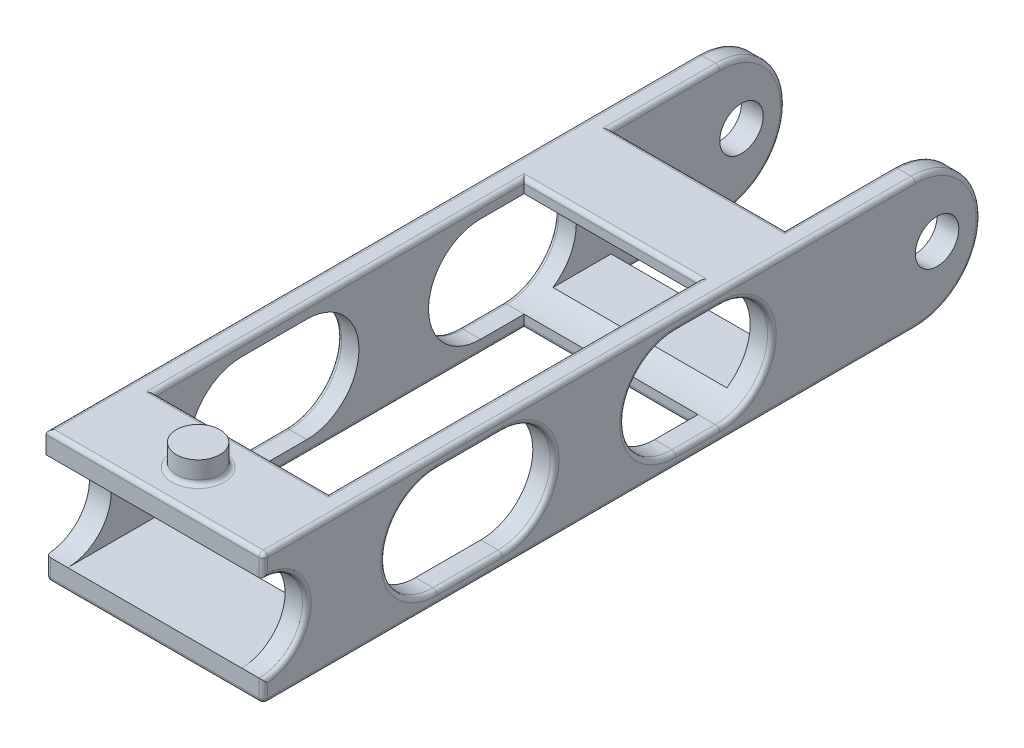
SolidWorks part; units mm, degrees
ref_plane "Front Plane" through (0, 0, 0) normal (0, 0, 1) x (1, 0, 0)
ref_plane "Top Plane" through (0, 0, 0) normal (0, 1, 0) x (1, 0, 0)
ref_plane "Right Plane" through (0, 0, 0) normal (1, 0, 0) x (0, 0, -1)
sketch "Sketch2" plane through (0, 0, 0) normal (1, 0, 0) x (0, 0, -1)
  line L1 (37.5, 7.5) -> (-37.5, 7.5)
  line L2 (37.5, 7.5) -> (37.5, -7.5)
  line L3 (37.5, -7.5) -> (-37.5, -7.5)
  line L4 (-37.5, 7.5) -> (-37.5, -7.5)
  line L5 (37.5, 7.5) -> (-37.5, -7.5) construction
  line L6 (37.5, -7.5) -> (-37.5, 7.5) construction
  arc A0 (37.5, 7.5) -> (37.5, -7.5) centre (37.5, 0) cw
  point P0 (0, 0)
  dimension "D1" = 75
  dimension "D2" = 15
extrude "Boss-Extrude1" add sketch "Sketch2" against normal blind 2.5 contours L1 L4 L3 L2 | A0 L2 region at (0, 0, 0) region at (0, 0, -40.6831)
ref_plane "Plane1" through (-12.5, 0, 0) normal (1, 0, 0) x (0, 0, -1)
sketch "Sketch3" plane through (0, 7.5, 0) normal (0, 1, 0) x (1, 0, 0)
  line L0 (-2.5, 37.5) -> (-2.5, -37.5) construction
  line L1 (-2.5, 25) -> (-22.5, 25)
  line L2 (-2.5, 25) -> (-2.5, 15)
  line L3 (-2.5, 15) -> (-22.5, 15)
  line L4 (-22.5, 25) -> (-22.5, 15)
  point P6 (-2.5, 20)
  dimension "D1" = 10
  dimension "D2" = 20
  dimension "D3" = 20
extrude "Boss-Extrude2" add sketch "Sketch3" against normal blind 2.5
mirror "Mirror2" about plane through (-12.5, 0, 0) normal (1, 0, 0) of "Boss-Extrude1"
sketch "Sketch5" plane through (0, 0, 0) normal (1, 0, 0) x (0, 0, -1)
  circle A0 centre (40, 0) radius 2.5
  dimension "D1" = 5
  dimension "D2" = 40
extrude "Cut-Extrude1" cut sketch "Sketch5" against normal through all
mirror "Mirror3" about plane through (0, 0, 0) normal (0, 1, 0) of "Boss-Extrude2"
sketch "Sketch6" plane through (0, 0, 0) normal (1, 0, 0) x (0, 0, -1)
  line L0 (-17.5, 0) -> (-10, 0) construction
  line L1 (-17.5, 6) -> (-10, 6)
  line L2 (-17.5, -6) -> (-10, -6)
  line L3 (10, 0) -> (15, 0) construction
  line L4 (10, 6) -> (15, 6)
  line L5 (10, -6) -> (15, -6)
  line L6 (-37.5, 7.5) -> (-37.5, -7.5) construction
  arc A1 (-17.5, 6) -> (-17.5, -6) centre (-17.5, 0) ccw
  arc A2 (-10, -6) -> (-10, 6) centre (-10, 0) ccw
  arc A3 (10, 6) -> (10, -6) centre (10, 0) ccw
  arc A4 (15, -6) -> (15, 6) centre (15, 0) ccw
  circle A6 centre (-37.5, 0) radius 5
  point P4 (-13.75, 0)
  point P10 (12.5, 0)
  dimension "D3" = 6
  dimension "D4" = 10
  dimension "D5" = 6
  dimension "D7" = 10
  dimension "D1" = 10
  dimension "D2" = 7.5
  dimension "D6" = 5
extrude "Cut-Extrude2" cut sketch "Sketch6" against normal through all
sketch "Sketch8" plane through (0, 7.5, 0) normal (0, 1, 0) x (1, 0, 0)
  line L0 (-2.5, 15) -> (-2.5, -37.5) construction
  line L1 (-22.5, -37.5) -> (-2.5, -37.5)
  line L2 (-22.5, -37.5) -> (-22.5, -27.5)
  line L3 (-22.5, -27.5) -> (-2.5, -27.5)
  line L4 (-2.5, -37.5) -> (-2.5, -27.5)
  dimension "D1" = 10
extrude "Boss-Extrude4" add sketch "Sketch8" against normal blind 2.5
mirror "Mirror5" about plane through (0, 0, 0) normal (0, 1, 0) of "Boss-Extrude4"
sketch "Sketch9" plane through (0, 7.5, 0) normal (0, 1, 0) x (1, 0, 0)
  line L0 (-12.5, -8.25) -> (-12.5, 8.25) construction
  line L1 (-25, -37.5) -> (0, -37.5) construction
  circle A0 centre (-12.5, -32.5) radius 2.5
  dimension "D1" = 5
  dimension "D2" = 5
extrude "Boss-Extrude5" add sketch "Sketch9" along normal blind 2.5
fillet "Fillet2" radius 0.5 14 edges at (0, 0, 23.5) (0, 6, 13.75) (0, 0, 4) (0, 0, -4) (0, 6, -12.5) (0, 0, -21) (0, -7.5, 0) (0, 0, -45) (0, -6, 13.75) (0, -6, -12.5) (0, -6.25, 37.5) (0, 0, 32.5) (0, 6.25, 37.5) (0, 7.5, 0)
fillet "Fillet3" radius 0.5 17 edges at (-25, -7.5, 0) (-25, 0, -45) (-22.5, -7.5, -31.25) (-22.5, 0, -45) (-2.5, -7.5, -31.25) (-2.5, 0, -45) (-0.1464, 7.3536, 37.3536) (-2.5, 7.5, 6.25) (-12.5, 7.5, -15) (-22.5, 7.5, 6.25) (-12.5, 7.5, 27.5) (-25, 7.5, 0) (-22.5, 7.5, -31.25) (-12.5, 7.5, -25) (-2.5, 7.5, -31.25) (-12.75, 7.5, 37.5) (-12.5, 7.5, 35)
fillet "Fillet6" radius 0.5 9 edges at (-25, -6, 37.5) (-24.8536, -7.3536, 37.5) (-0.1464, -7.3536, 37.3536) (-12.5, -7.5, -15) (-2.5, -7.5, 6.25) (-12.5, -7.5, 27.5) (-22.5, -7.5, 6.25) (-12.5, -7.5, -25) (-12.5, -7.5, 37.5)
fillet "Fillet7" radius 0.5 8 edges at (-25, 0, -4) (-25, 6, -12.5) (-25, 0, -21) (-25, -6, 13.75) (-25, 0, 23.5) (-25, 6, 13.75) (-25, -6, -12.5) (-25, 0, 4)
